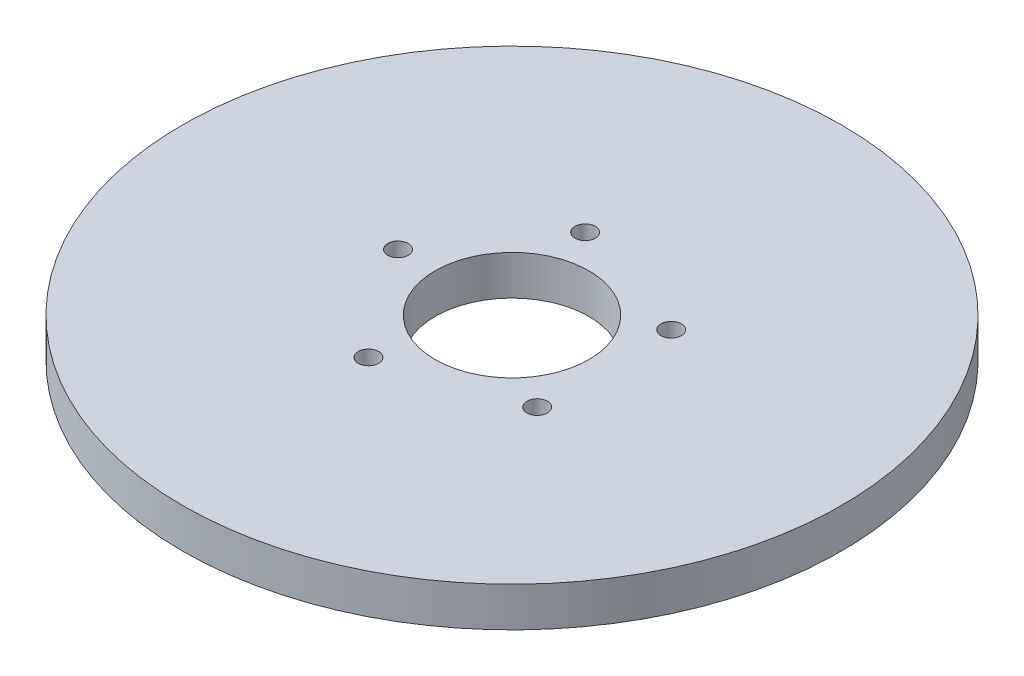
SolidWorks part; units mm, degrees
ref_plane "Front Plane" through (0, 0, 0) normal (0, 0, 1) x (1, 0, 0)
ref_plane "Top Plane" through (0, 0, 0) normal (0, 1, 0) x (1, 0, 0)
ref_plane "Right Plane" through (0, 0, 0) normal (1, 0, 0) x (0, 0, -1)
sketch "Sketch1" plane through (0, 0, 0) normal (0, 1, 0) x (1, 0, 0)
  circle A0 centre (0, 0) radius 75
  dimension "FLANGE_OD" = 150
extrude "Boss-Extrude1" add sketch "Sketch1" along normal blind 9
sketch "Sketch2" plane through (0, 0, 0) normal (0, 1, 0) x (1, 0, 0)
  circle A0 centre (0, 0) radius 17.5
  dimension "BORE_D" = 35
extrude "Cut-Extrude1" cut sketch "Sketch2" along normal through all
sketch "Sketch3" plane through (0, 9, 0) normal (0, 1, 0) x (1, 0, 0)
  circle A0 centre (0, 0) radius 25.9378 construction
  circle A1 centre (-25.9378, 0) radius 2.3324
  dimension "BOLT_D" = 4.6648
  dimension "BOLT_PCD" = 51.8756
extrude "Cut-Extrude2" cut sketch "Sketch3" against normal blind 8.5664
pattern_circular "CirPattern1" count 5 over 360 about axis through (0, 0, 0) along (0, 1, 0) of "Cut-Extrude2"
